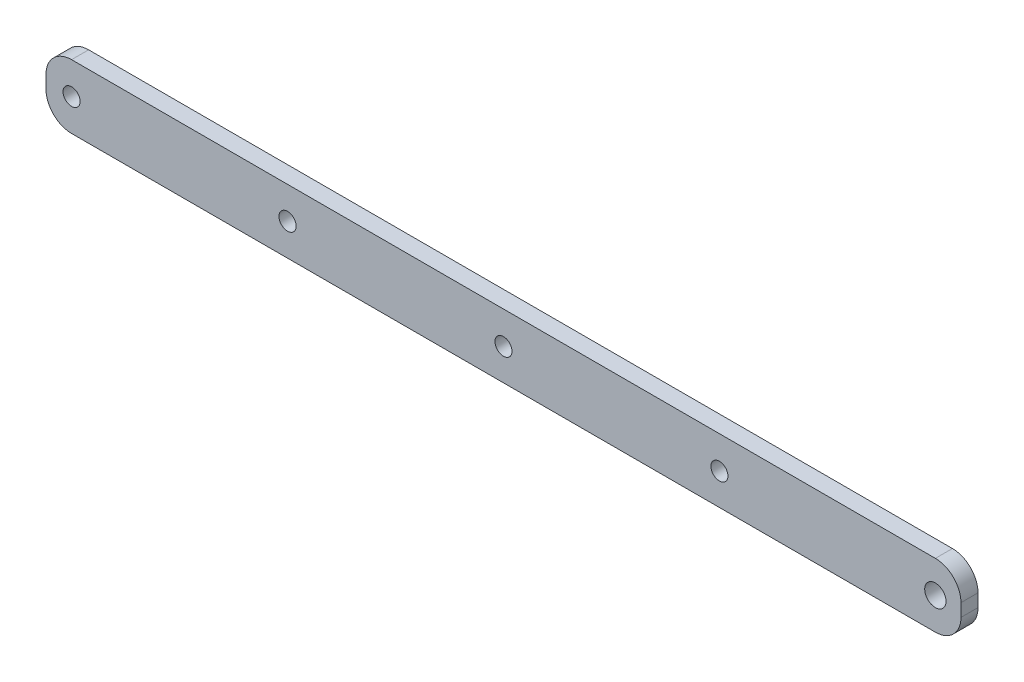
SolidWorks part; units mm, degrees
material "ABS PC"
ref_plane "Front Plane" through (0, 0, 0) normal (0, 0, 1) x (1, 0, 0)
ref_plane "Top Plane" through (0, 0, 0) normal (0, 1, 0) x (1, 0, 0)
ref_plane "Right Plane" through (0, 0, 0) normal (1, 0, 0) x (0, 0, -1)
sketch "Sketch1" plane through (0, 0, 0) normal (0, 0, 1) x (1, 0, 0)
  line L1 (7.62, 0) -> (264.922, 0)
  line L2 (0, 7.62) -> (0, 11.43)
  line L3 (7.62, 19.05) -> (264.922, 19.05)
  line L4 (272.542, 7.62) -> (272.542, 11.43)
  circle A0 centre (264.922, 9.525) radius 3.175
  circle A1 centre (7.62, 9.525) radius 2.54
  arc A2 (264.922, 0) -> (272.542, 7.62) centre (264.922, 7.62) ccw
  arc A3 (7.62, 0) -> (0, 7.62) centre (7.62, 7.62) cw
  arc A4 (264.922, 19.05) -> (272.542, 11.43) centre (264.922, 11.43) cw
  arc A5 (0, 11.43) -> (7.62, 19.05) centre (7.62, 11.43) cw
  circle A6 centre (71.9455, 9.525) radius 2.5586
  circle A7 centre (136.271, 9.398) radius 2.54
  circle A8 centre (200.5965, 9.398) radius 2.54
  point P13 (0, 0)
  point P24 (71.5592, 16.5638)
  point P25 (90.7159, 8.9389)
  point P26 (71.9455, 9.525)
  point P27 (159.0051, 9.398)
  dimension "D3" = 5.08
  dimension "D4" = 6.35
  dimension "D9" = 7.62
  dimension "D10" = 5.1173
  dimension "D11" = 5.08
  dimension "D12" = 5.08
  dimension "D14" = 9.525
  dimension "D1" = 257.302
  dimension "D2" = 19.05
  dimension "D5" = 9.525
  dimension "D6" = 7.62
  dimension "D7" = 7.62
  dimension "D8" = 9.525
  dimension "D13" = 64.3255
  dimension "D15" = 64.3255
  dimension "D16" = 9.652
  dimension "D17" = 64.3255
  dimension "D18" = 9.652
extrude "Boss-Extrude1" add sketch "Sketch1" along normal blind 5.08
